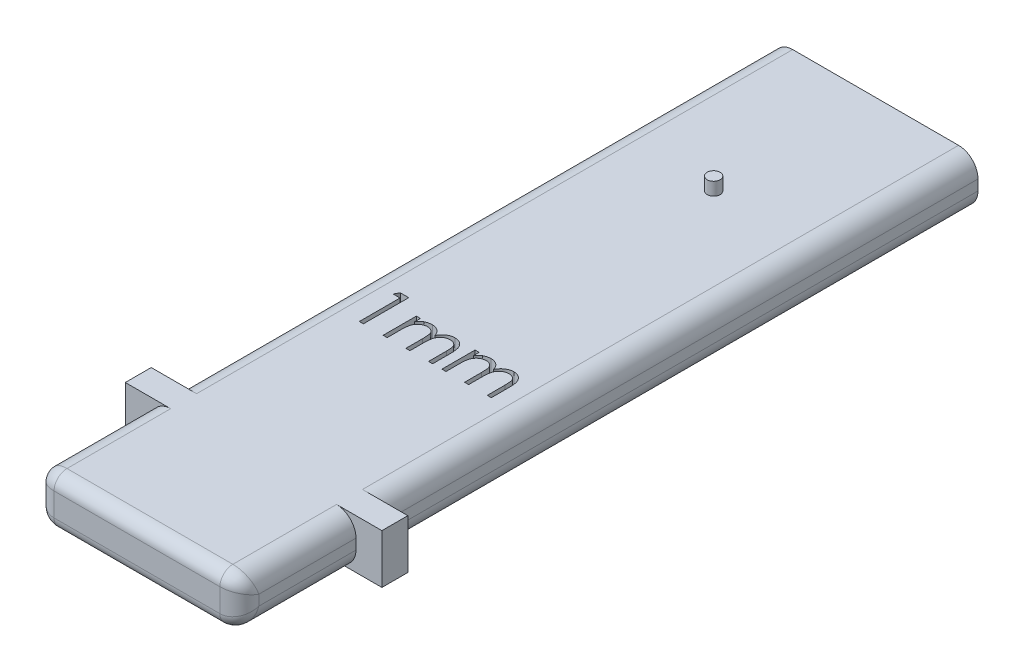
SolidWorks part; units mm, degrees
ref_plane "Front Plane" through (0, 0, 0) normal (0, 0, 1) x (1, 0, 0)
ref_plane "Top Plane" through (0, 0, 0) normal (0, 1, 0) x (1, 0, 0)
ref_plane "Right Plane" through (0, 0, 0) normal (1, 0, 0) x (0, 0, -1)
sketch "Sketch2" plane through (0, 0, 0) normal (0, 1, 0) x (1, 0, 0)
  line L1 (0, 0) -> (15.8, 0)
  line L2 (0, 0) -> (0, 57)
  line L3 (0, 57) -> (15.8, 57)
  line L4 (15.8, 0) -> (15.8, 57)
  dimension "D1" = 57
  dimension "D2" = 15.8
extrude "Boss-Extrude1" add sketch "Sketch2" along normal blind 3.8
fillet "Fillet3" radius 1 2 edges at (7.9, 0, 0) (7.9, 3.8, 0)
sketch "Sketch5" plane through (0, 3.8, 0) normal (0, 1, 0) x (1, 0, 0)
  line L0 (15.8, 57) -> (0, 57) construction
  circle A0 centre (7.9, 44.5) radius 0.5
  point P4 (7.9, 57)
  dimension "D1" = 1
  dimension "D2" = 12.5
extrude "Boss-Extrude4" add sketch "Sketch5" along normal blind 1
sketch "Sketch6" plane through (15.8, 0, 0) normal (1, 0, 0) x (0, 0, -1)
  line L0 (9, 3.8) -> (9, 0)
  line L1 (1, 3.8) -> (57, 3.8) construction
  line L2 (1, 0) -> (57, 0) construction
  line L3 (9, 0) -> (11, 0)
  line L4 (11, 0) -> (11, 3.8)
  line L5 (11, 3.8) -> (9, 3.8)
  line L6 (0, 2.8) -> (0, 1) construction
  dimension "D1" = 9
  dimension "D2" = 2
extrude "Boss-Extrude5" add sketch "Sketch6" along normal blind 2
sketch "Sketch7" plane through (0, 0, 0) normal (-1, 0, 0) x (0, 0, 1)
  line L0 (-57, 0) -> (-1, 0) construction
  line L1 (-9, 0) -> (-11, 0)
  line L2 (-9, 0) -> (-9, 3.8)
  line L3 (-9, 3.8) -> (-11, 3.8)
  line L4 (-11, 0) -> (-11, 3.8)
  line L5 (-57, 3.8) -> (-1, 3.8) construction
  line L6 (0, 2.8) -> (0, 1) construction
  dimension "D1" = 9
  dimension "D2" = 2
extrude "Boss-Extrude6" add sketch "Sketch7" along normal blind 2
fillet "Fillet4" radius 1.5 14 edges at (0, 0.2929, -0.2929) (0, 1.9, 0) (0, 3.5071, -0.2929) (15.8, 0.2929, -0.2929) (15.8, 1.9, 0) (15.8, 3.5071, -0.2929) (0, 0, -34) (0, 0, -5) (0, 3.8, -5) (0, 3.8, -34) (15.8, 0, -34) (15.8, 3.8, -34) (15.8, 0, -5) (15.8, 3.8, -5)
sketch "Sketch9" plane through (0, 3.8, 0) normal (0, 1, 0) x (1, 0, 0)
  text T0 "1mm"
extrude "Cut-Extrude1" cut sketch "Sketch9" against normal blind 5
